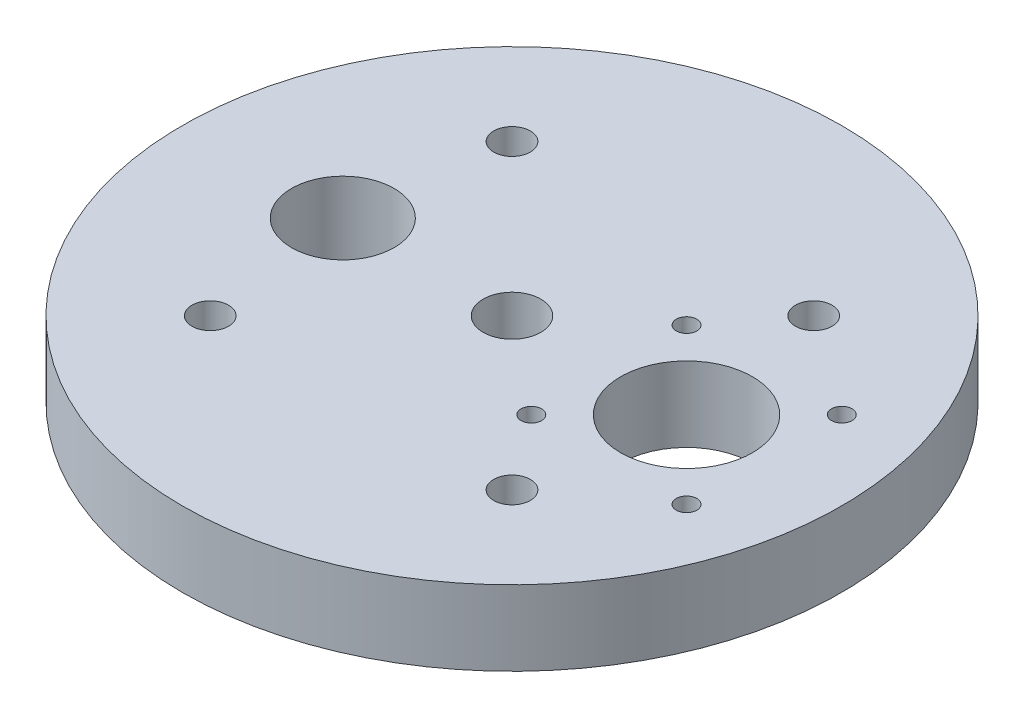
SolidWorks part; units mm, degrees
ref_plane "Front Plane" through (0, 0, 0) normal (0, 0, 1) x (1, 0, 0)
ref_plane "Top Plane" through (0, 0, 0) normal (0, 1, 0) x (1, 0, 0)
ref_plane "Right Plane" through (0, 0, 0) normal (1, 0, 0) x (0, 0, -1)
sketch "Sketch2" plane through (0, 0, 0) normal (0, 1, 0) x (1, 0, 0)
  circle A0 centre (0, 0) radius 57.15
  dimension "D1" = 114.3
extrude "Boss-Extrude1" add sketch "Sketch2" along normal blind 13 contours A0
sketch "Sketch6" plane through (0, 13, 0) normal (0, 1, 0) x (1, 0, 0)
  circle A0 centre (-26.1629, -26.1629) radius 3.175
  circle A1 centre (26.1629, -26.1629) radius 3.175
  circle A2 centre (-26.1629, 26.1631) radius 3.175
  circle A3 centre (26.1629, 26.1631) radius 3.175
  dimension "D1" = 6.35
  dimension "D2" = 74
  dimension "D3" = 26.1629
  dimension "D4" = 26.1629
  dimension "D5" = 26.1629
extrude "Cut-Extrude1" cut sketch "Sketch6" against normal up to next
sketch "Sketch7" plane through (0, 13, 0) normal (0, 1, 0) x (1, 0, 0)
  circle A0 centre (30, 0.2699) radius 11.43
  circle A3 centre (16.54, -13.1941) radius 1.778
  circle A4 centre (16.54, 13.7299) radius 1.778
  circle A5 centre (43.46, 13.7299) radius 1.778
  circle A6 centre (43.46, -13.1941) radius 1.778
  dimension "D1" = 22.86
  dimension "D2" = 3.556
  dimension "D3" = 3.556
  dimension "D4" = 3.556
  dimension "D5" = 3.556
  dimension "D6" = 13.46
  dimension "D7" = 13.46
  dimension "D8" = 13.46
  dimension "D9" = 13.464
  dimension "D10" = 30
extrude "Cut-Extrude2" cut sketch "Sketch7" against normal through all
sketch "Sketch8" plane through (0, 13, 0) normal (0, 1, 0) x (1, 0, 0)
  circle A2 centre (0, 0) radius 5
  circle A3 centre (-29.3379, 0) radius 8.9
  dimension "D3" = 10
  dimension "D4" = 17.8
extrude "Cut-Extrude3" cut sketch "Sketch8" against normal through all
equation "\"width\"=26.1629"
equation "\"D4@Sketch6\"=\"width\""
equation "\"D3@Sketch6\"=\"width\""
equation "\"D5@Sketch6\"=\"width\""
